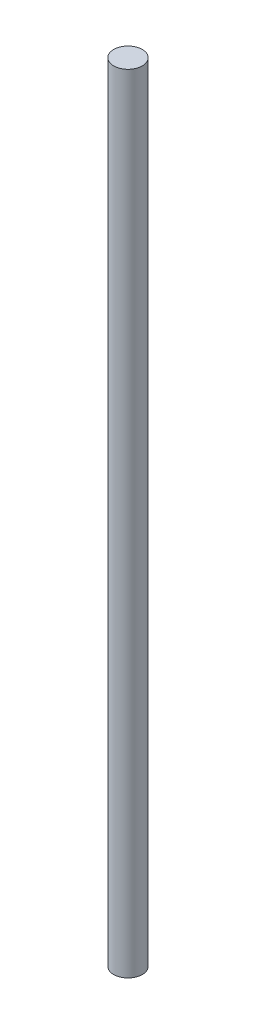
SolidWorks part; units mm, degrees
material "Chrome Stainless Steel"
ref_plane "Front Plane" through (0, 0, 0) normal (0, 0, 1) x (1, 0, 0)
ref_plane "Top Plane" through (0, 0, 0) normal (0, 1, 0) x (1, 0, 0)
ref_plane "Right Plane" through (0, 0, 0) normal (1, 0, 0) x (0, 0, -1)
sketch "Sketch1" plane through (0, 0, 0) normal (0, 1, 0) x (1, 0, 0)
  circle A0 centre (0, 0) radius 3.175
extrude "Boss-Extrude1" add sketch "Sketch1" along normal blind 174.953
